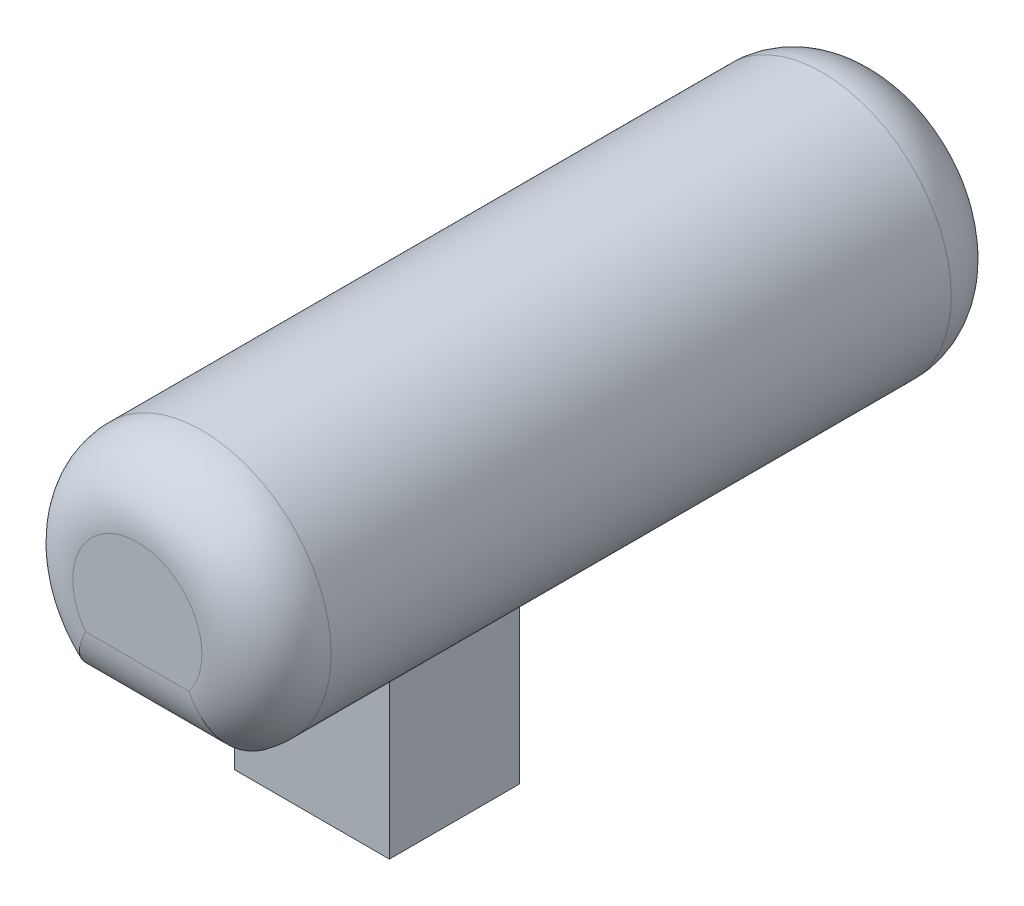
SolidWorks part; units mm, degrees
ref_plane "Alzado" through (0, 0, 0) normal (0, 0, 1) x (1, 0, 0)
ref_plane "Planta" through (0, 0, 0) normal (0, 1, 0) x (1, 0, 0)
ref_plane "Vista lateral" through (0, 0, 0) normal (1, 0, 0) x (0, 0, -1)
sketch "Croquis2" plane through (0, 0, 0) normal (0, 0, 1) x (1, 0, 0)
  line L2 (-3, -4) -> (-3, -10)
  line L3 (-3, -10) -> (3, -10)
  line L4 (3, -4) -> (3, -10)
  arc A0 (3, -4) -> (-3, -4) centre (0, 0) ccw
  point P3 (0.255, -9.2609)
  dimension "D3" = 5
  dimension "D1" = 6
  dimension "D2" = 6
  dimension "D4" = 6
extrude "Saliente-Extruir1" add sketch "Croquis2" along normal blind 29
sketch "Croquis5" plane through (0, 0, 0) normal (1, 0, 0) x (0, 0, -1)
  line L0 (-33.0577, -10) -> (1.9423, -10) construction
  line L2 (-20.0555, -18.3881) -> (-11.0555, -18.3881) construction
  line L6 (-29, -10) -> (-29, -4)
  line L7 (-29, -4) -> (-22.2454, -4)
  line L8 (-29, -4) -> (0, -4) construction
  line L9 (-22.2454, -4) -> (-22.2454, -10)
  line L10 (-22.2454, -10) -> (-29, -10)
  dimension "D1" = 29
  dimension "D2" = 9
extrude "Cortar-Extruir7" cut sketch "Croquis5" against normal through all both and the other way through all
sketch "Croquis9" plane through (3, 0, 0) normal (1, 0, 0) x (0, 0, -1)
  line L0 (-17.2093, -4) -> (-17.2093, -10)
  line L1 (-22.2454, -4) -> (0, -4) construction
  line L2 (-22.2454, -10) -> (0, -10) construction
  line L3 (-17.2093, -10) -> (0, -10)
  line L4 (0, -10) -> (0, -4)
  line L5 (0, -4) -> (-17.2093, -4)
extrude "Cortar-Extruir8" cut sketch "Croquis9" against normal through all both and the other way through all
fillet "Redondeo3" radius 2.5 4 edges at (0, 5, 29) (0, -4, 29) (0, -4, 0) (0, 5, 0)
